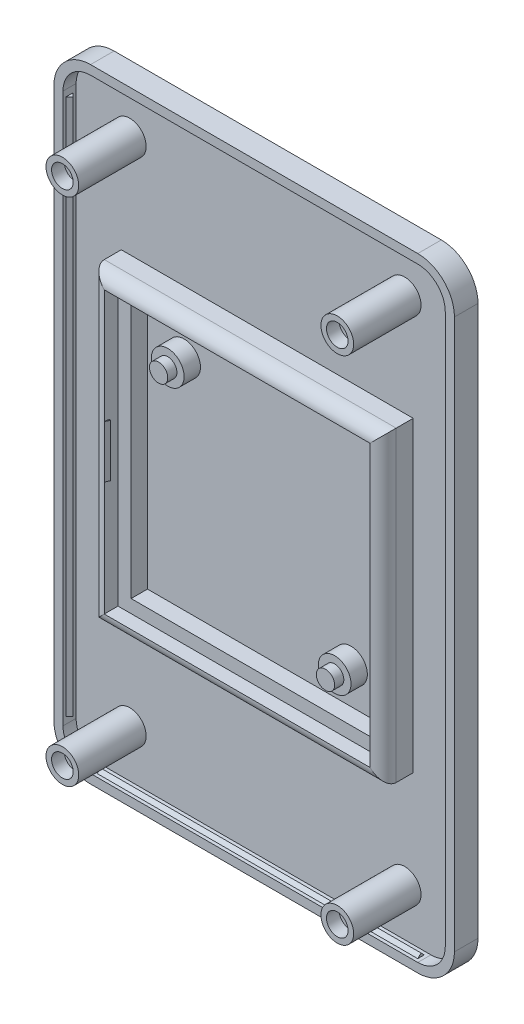
SolidWorks part; units mm, degrees
ref_plane "Front Plane" through (0, 0, 0) normal (0, 0, 1) x (1, 0, 0)
ref_plane "Top Plane" through (0, 0, 0) normal (0, 1, 0) x (1, 0, 0)
ref_plane "Right Plane" through (0, 0, 0) normal (1, 0, 0) x (0, 0, -1)
sketch "Esquisse2" plane through (0, 0, 0) normal (0, 0, 1) x (1, 0, 0)
  line L1 (-29.2, -46.2) -> (29.2, -46.2)
  line L2 (-29.2, -46.2) -> (-29.2, 46.2)
  line L3 (-29.2, 46.2) -> (29.2, 46.2)
  line L4 (29.2, -46.2) -> (29.2, 46.2)
  line L5 (-29.2, -46.2) -> (29.2, 46.2) construction
  line L6 (-29.2, 46.2) -> (29.2, -46.2) construction
  point P0 (0, 0)
  dimension "D1" = 92.4
  dimension "D2" = 58.4
extrude "Boss.-Extru.1" add sketch "Esquisse2" against normal blind 1.6
fillet "Congé1" radius 4.2 4 edges at (-29.2, 46.2, -0.8) (29.2, 46.2, -0.8) (29.2, -46.2, -0.8) (-29.2, -46.2, -0.8)
sketch "Esquisse3" plane through (0, 0, 0) normal (0, 0, 1) x (1, 0, 0)
  line L1 (20.3, -21.45) -> (-20.3, -21.45)
  line L2 (20.3, -21.45) -> (20.3, 21.45)
  line L3 (20.3, 21.45) -> (-20.3, 21.45)
  line L4 (-20.3, -21.45) -> (-20.3, 21.45)
  line L5 (20.3, -21.45) -> (-20.3, 21.45) construction
  line L6 (20.3, 21.45) -> (-20.3, -21.45) construction
  point P0 (0, 0)
  dimension "D1" = 42.9
  dimension "D2" = 40.6
extrude "Extru.-Mince1" add sketch "Esquisse3" along normal blind 2.5 thin contours L4 L3 L2 L1 thin type one direction reverse wall 2
sketch "Esquisse4" plane through (0, 0, 0) normal (0, 0, 1) x (1, 0, 0)
  line L0 (20.3, 21.45) -> (-20.3, 21.45) construction
  line L1 (-12.7, 13.95) -> (-20.2, 13.95)
  line L2 (-12.7, 13.95) -> (-12.7, 21.45)
  line L3 (-12.7, 21.45) -> (-20.2, 21.45)
  line L4 (-20.2, 13.95) -> (-20.2, 21.45)
  line L5 (-12.7, 13.95) -> (-20.2, 21.45) construction
  line L6 (-12.7, 21.45) -> (-20.2, 13.95) construction
  circle A0 centre (-12.7, 13.95) radius 2.5
  point P0 (-16.45, 17.7)
  dimension "D1" = 7.5
  dimension "D2" = 7.5
extrude "Boss.-Extru.2" add sketch "Esquisse4" along normal blind 2.5 contours A0
sketch "Esquisse5" plane through (0, 0, 0) normal (0, 0, 1) x (1, 0, 0)
  circle A0 centre (-12.7, 13.95) radius 1.4
extrude "Boss.-Extru.3" add sketch "Esquisse5" along normal blind 3.9
sketch "Esquisse6" plane through (0, 0, 0) normal (0, 0, 1) x (1, 0, 0)
  line L1 (20.3, -21.45) -> (12.8, -21.45) construction
  line L2 (20.3, -21.45) -> (20.3, -13.95) construction
  line L3 (20.3, -13.95) -> (12.8, -13.95) construction
  line L4 (12.8, -21.45) -> (12.8, -13.95)
  circle A0 centre (12.8, -13.95) radius 2.5
  dimension "D1" = 7.5
  dimension "D2" = 7.5
extrude "Boss.-Extru.4" add sketch "Esquisse6" along normal blind 2.5 contours A0
sketch "Esquisse7" plane through (0, 0, 0) normal (0, 0, 1) x (1, 0, 0)
  circle A0 centre (12.8, -13.95) radius 1.4
extrude "Boss.-Extru.5" add sketch "Esquisse7" along normal blind 3.9 contours A0
sketch "Esquisse8" plane through (0, 0, 0) normal (0, 0, 1) x (1, 0, 0)
  line L1 (20.3, -21.45) -> (-20.3, -21.45)
  line L2 (20.3, -21.45) -> (20.3, 21.45)
  line L3 (20.3, 21.45) -> (-20.3, 21.45)
  line L4 (-20.3, -21.45) -> (-20.3, 21.45)
extrude "Extru.-Mince2" add sketch "Esquisse8" along normal blind 4.6 thin thin type one direction wall 2
fillet "Congé2" radius 2 4 edges at (22.3, 0, 4.6) (0, 23.45, 4.6) (-22.3, 0, 4.6) (0, -23.45, 4.6)
sketch "Esquisse10" plane through (0, 0, 0) normal (0, 0, 1) x (1, 0, 0)
  line L1 (21, -39) -> (-21, -39)
  line L2 (21, -39) -> (21, 39)
  line L3 (21, 39) -> (-21, 39)
  line L4 (-21, -39) -> (-21, 39)
  line L5 (21, -39) -> (-21, 39) construction
  line L6 (21, 39) -> (-21, -39) construction
  circle A0 centre (21, -39) radius 2.5
  circle A1 centre (-21, -39) radius 2.5
  circle A2 centre (-21, 39) radius 2.5
  circle A3 centre (21, 39) radius 2.5
  point P0 (0, 0)
  dimension "D1" = 78
  dimension "D2" = 42
extrude "Boss.-Extru.6" add sketch "Esquisse10" along normal blind 10.3 contours A1 | A0 | A3 | A2
sketch "Esquisse13" plane through (0, 0, 10.3) normal (0, 0, 1) x (1, 0, 0)
  circle A0 centre (21, -39) radius 1.65
  circle A1 centre (-21, -39) radius 1.65
  circle A2 centre (-21, 39) radius 1.65
  circle A3 centre (21, 39) radius 1.65
extrude "Enlèv. mat.-Extru.1" cut sketch "Esquisse13" against normal blind 1.95
sketch "Esquisse14" plane through (0, 0, 0) normal (0, 0, 1) x (1, 0, 0)
  line L0 (25, 46.2) -> (-25, 46.2) construction
  line L1 (29.2, -42) -> (29.2, 42) construction
  line L2 (-29.2, 42) -> (-29.2, -42) construction
  line L3 (-25, -46.2) -> (25, -46.2) construction
  line L4 (25, 46.2) -> (-25, 46.2)
  line L5 (29.2, -42) -> (29.2, 42)
  line L6 (-29.2, 42) -> (-29.2, -42)
  line L7 (-25, -46.2) -> (25, -46.2)
  arc A0 (-25, 46.2) -> (-29.2, 42) centre (-25, 42) ccw construction
  arc A1 (29.2, 42) -> (25, 46.2) centre (25, 42) ccw construction
  arc A2 (25, -46.2) -> (29.2, -42) centre (25, -42) ccw construction
  arc A3 (-29.2, -42) -> (-25, -46.2) centre (-25, -42) ccw construction
  arc A4 (-25, 46.2) -> (-29.2, 42) centre (-25, 42) ccw
  arc A5 (29.2, 42) -> (25, 46.2) centre (25, 42) ccw
  arc A6 (25, -46.2) -> (29.2, -42) centre (25, -42) ccw
  arc A7 (-29.2, -42) -> (-25, -46.2) centre (-25, -42) ccw
extrude "Extru.-Mince3" add sketch "Esquisse14" along normal blind 2 and the other way blind 1.6 thin thin type one direction wall 1.4
sketch3d "Esquisse3D7"
  line L0 (20.3, -21.45, 4.6) -> (20.3, 0, 4.6) construction
  line L1 (20.3, -21.45, 4.6) -> (20.3, 21.45, 4.6) construction
  line L2 (20.3, 0, 4.6) -> (20.3, 0, 3.9)
  line L3 (20.3, 0, 4.6) -> (20.05, 0, 3.9)
  line L4 (20.05, 0, 3.9) -> (20.3, 0, 3.9)
extrude "Boss.-Extru.9" add sketch "Esquisse3D7" along direction (0, 1, 0) on the side of the normal blind 4 and the other way blind 4 contours L3 L4 L2
sketch3d "Esquisse3D8"
  line L0 (-20.3, 0, 4.6) -> (-20.0062, 0, 3.9153)
  line L1 (-20.3, 21.45, 4.6) -> (-20.3, -21.45, 4.6) construction
  line L2 (-20.0062, 0, 3.9153) -> (-20.2371, 0, 3.8947)
  line L3 (-20.2371, 0, 3.8947) -> (-20.3, 0, 4.6)
extrude "Boss.-Extru.10" add sketch "Esquisse3D8" along direction (0, -1, 0) on the side of the normal blind 4 and the other way blind 4 separate body
sketch "Esquisse16" plane through (29.2, 0, 0) normal (-1, 0, 0) x (0, 0, 1)
  line L0 (2, 0) -> (0, 0)
  line L1 (2, -42) -> (2, 42) construction
  line L2 (0, -42) -> (0, 42) construction
sketch3d "Esquisse3D9"
  line L2 (29.2, 0, 1) -> (29.2, 0, 1.5111)
  line L3 (29.2, 0, 2) -> (29.2, 0, 0) construction
  line L4 (29.2, 0, 1) -> (29.2, 0, 0.4889)
  line L6 (20.3, -21.45, 4.6) -> (20.3, -4, 4.6) construction
  line L7 (29.2, 0, 1.5111) -> (28.6889, 0, 1)
  line L8 (28.6889, 0, 1) -> (29.2, 0, 0.4889)
extrude "Boss.-Extru.11" add sketch "Esquisse3D9" along direction (0, 1, 0) on the side of the normal blind 41 and the other way blind 41
mirror "Symétrie1" about plane through (0, 0, 0) normal (1, 0, 0) of "Boss.-Extru.11"
sketch "Esquisse19" plane through (0, 46.2, 0) normal (0, -1, 0) x (-1, 0, 0)
  line L0 (0, -2) -> (0, 0) construction
  line L1 (-25, -2) -> (25, -2) construction
  line L2 (-25, 0) -> (25, 0) construction
  line L3 (0, -1) -> (0, -1.5)
  line L4 (0, -1) -> (0, -0.5)
sketch3d "Esquisse3D12"
  line L2 (0, 46.2, 1.5) -> (0, 45.7, 1)
  line L3 (0, 45.7, 1) -> (0, 46.2, 0.5)
  line L5 (0, 46.2, 1.5) -> (0, 46.2, 0.5)
  dimension "D1" = 90
extrude "Boss.-Extru.12" add sketch "Esquisse3D12" along direction (-1, 0, 0) on the side of the normal blind 24.5 and the other way blind 24.5
mirror "Symétrie2" about plane through (0, 0, 0) normal (0, 1, 0) of "Boss.-Extru.12"
sketch "Esquisse31" plane through (0, 0, -1.6) normal (0, 0, -1) x (-1, 0, 0)
  spline S0 degree 3 poles (4.0392, -9.9887) (3.6583, -9.8345) (3.3861, -9.4898) (3.3227, -9.0816) knots 0 0 0 0 1 1 1 1
  spline S1 degree 3 poles (3.3227, -9.0816) (3.2773, -8.8458) (3.3227, -8.6825) (3.6855, -8.0295) knots 1 1 1 1 2 2 2 2
  spline S2 degree 3 poles (3.6855, -8.0295) (5.046, -5.5805) (5.7444, -2.8141) (5.7081, -0.0113) knots 2 2 2 2 3 3 3 3
  spline S3 degree 3 poles (5.7081, -0.0113) (5.7444, 2.7098) (5.0823, 5.3673) (3.7762, 7.7528) knots 3 3 3 3 4 4 4 4
  spline S4 degree 3 poles (3.7762, 7.7528) (3.5857, 8.1519) (3.4134, 8.5329) (3.2682, 8.941) knots 4 4 4 4 5 5 5 5
  spline S5 degree 3 poles (3.2682, 8.941) (3.3227, 9.2857) (3.495, 9.6032) (3.7762, 9.7937) knots 5 5 5 5 6 6 6 6
  spline S6 degree 3 poles (3.7762, 9.7937) (4.1843, 10.0113) (4.6832, 9.966) (5.0551, 9.712) knots 6 6 6 6 7 7 7 7
  spline S7 degree 3 poles (5.0551, 9.712) (5.309, 9.3855) (5.5267, 9.059) (5.7081, 8.678) knots 7 7 7 7 8 8 8 8
  spline S8 degree 3 poles (5.7081, 8.678) (6.6877, 6.7914) (7.3499, 4.7959) (7.6764, 2.7098) knots 8 8 8 8 9 9 9 9
  spline S9 degree 3 poles (7.6764, 2.7098) (7.885, 1.068) (7.9122, -0.6009) (7.758, -2.2517) knots 9 9 9 9 10 10 10 10
  spline S10 degree 3 poles (7.758, -2.2517) (7.4768, -4.3741) (6.851, -6.424) (5.8895, -8.3379) knots 10 10 10 10 11 11 11 11
  spline S11 degree 3 poles (5.8895, -8.3379) (5.309, -9.4989) (4.9825, -9.9887) (4.6378, -9.9887) knots 11 11 11 11 12 12 12 12
  spline S12 degree 3 poles (4.6378, -9.9887) (4.5653, -9.9887) (4.4837, -9.9887) (4.4111, -9.9887) knots 12 12 12 12 13 13 13 13
  spline S13 degree 3 poles (4.4111, -9.9887) (4.2841, -9.9887) (4.1662, -9.9887) (4.0392, -9.9887) knots 13 13 13 13 14 14 14 14
  spline S14 degree 3 poles (0.0846, -7.9388) (0.0846, -7.9539) (0.0846, -7.969) (0.0846, -7.9841) knots 9 9 9 9 10 10 10 10
  spline S15 degree 3 poles (2.1344, -5.907) (1.3725, -7.6213) (0.8374, -8.1746) (0.0846, -7.9388) knots 8 8 8 8 9 9 9 9
  spline S16 degree 3 poles (2.6424, 4.5782) (3.8034, 1.1406) (3.622, -2.6054) (2.1344, -5.907) knots 7 7 7 7 8 8 8 8
  spline S17 degree 3 poles (1.0914, 7.6984) (1.7444, 6.737) (2.2614, 5.6848) (2.6424, 4.5782) knots 6 6 6 6 7 7 7 7
  spline S18 degree 3 poles (-0.4597, 7.5714) (-0.0606, 8.0159) (0.6016, 8.0794) (1.0914, 7.6984) knots 5 5 5 5 6 6 6 6
  spline S19 degree 3 poles (-0.1876, 5.7574) (-0.759, 6.9002) (-0.7953, 7.0816) (-0.4597, 7.5714) knots 4 4 4 4 5 5 5 5
  spline S20 degree 3 poles (1.2093, 1.0227) (1.0823, 2.6825) (0.6016, 4.2971) (-0.1876, 5.7574) knots 3 3 3 3 4 4 4 4
  spline S21 degree 3 poles (-0.115, -5.6712) (0.9553, -3.6122) (1.4179, -1.2902) (1.2093, 1.0227) knots 2 2 2 2 3 3 3 3
  spline S22 degree 3 poles (-0.6501, -6.7868) (-0.6501, -6.678) (-0.369, -6.1791) (-0.115, -5.6712) knots 1 1 1 1 2 2 2 2
  spline S23 degree 3 poles (0.0846, -7.9841) (-0.4324, -7.839) (-0.759, -7.3129) (-0.6501, -6.7868) knots 0 0 0 0 1 1 1 1
  spline S24 degree 3 poles (-3.9971, -5.907) (-3.9971, -5.9252) (-3.9971, -5.9433) (-3.9971, -5.9615) knots 10 10 10 10 11 11 11 11
  spline S25 degree 3 poles (-3.4801, -5.9887) (-3.6524, -6.0068) (-3.8338, -5.9887) (-3.9971, -5.907) knots 9 9 9 9 10 10 10 10
  spline S26 degree 3 poles (-2.2556, -4.7279) (-2.7454, -5.6803) (-2.9903, -5.907) (-3.4801, -5.9887) knots 8 8 8 8 9 9 9 9
  spline S27 degree 3 poles (-1.1037, -0.0113) (-1.0674, -1.6531) (-1.4665, -3.2857) (-2.2556, -4.7279) knots 7 7 7 7 8 8 8 8
  spline S28 degree 3 poles (-2.2646, 4.6054) (-1.4937, 3.1905) (-1.0946, 1.6032) (-1.1037, -0.0113) knots 6 6 6 6 7 7 7 7
  spline S29 degree 3 poles (-3.6615, 5.9116) (-3.081, 5.9116) (-2.7544, 5.6304) (-2.2646, 4.6054) knots 5 5 5 5 6 6 6 6
  spline S30 degree 3 poles (-4.3599, 5.6485) (-4.1876, 5.8481) (-3.9336, 5.9478) (-3.6615, 5.9116) knots 4 4 4 4 5 5 5 5
  spline S31 degree 3 poles (-4.251, 3.8345) (-4.8406, 4.9773) (-4.8406, 5.2132) (-4.3599, 5.6485) knots 3 3 3 3 4 4 4 4
  spline S32 degree 3 poles (-4.251, -4.0385) (-2.8996, -1.5896) (-2.8996, 1.3855) (-4.251, 3.8345) knots 2 2 2 2 3 3 3 3
  spline S33 degree 3 poles (-4.6592, -5.1814) (-4.6592, -5) (-4.6592, -4.7642) (-4.251, -4.0385) knots 1 1 1 1 2 2 2 2
  spline S34 degree 3 poles (-3.9971, -5.9615) (-4.3236, -5.8163) (-4.5685, -5.5261) (-4.6592, -5.1814) knots 0 0 0 0 1 1 1 1
  spline S35 degree 3 poles (-7.8066, -4.0295) (-7.8096, -4.0295) (-7.8126, -4.0295) (-7.8157, -4.0295) knots 9 9 9 9 10 10 10 10
  spline S36 degree 3 poles (-6.2737, -3.3039) (-6.7363, -4.0023) (-7.2624, -4.2109) (-7.8066, -4.0295) knots 8 8 8 8 9 9 9 9
  spline S37 degree 3 poles (-6.2737, 3.2902) (-4.9585, 1.2857) (-4.9585, -1.2993) (-6.2737, -3.3039) knots 7 7 7 7 8 8 8 8
  spline S38 degree 3 poles (-7.5617, 4.0975) (-7.0719, 4.1882) (-6.7272, 3.9796) (-6.2737, 3.2902) knots 6 6 6 6 7 7 7 7
  spline S39 degree 3 poles (-8.4687, 2.873) (-8.5685, 3.4444) (-8.1876, 3.9887) (-7.5617, 4.0975) knots 5 5 5 5 6 6 6 6
  spline S40 degree 3 poles (-8.0696, 2.1565) (-8.2238, 2.3832) (-8.3508, 2.6281) (-8.4687, 2.873) knots 4 4 4 4 5 5 5 5
  spline S41 degree 3 poles (-7.4801, -0.0113) (-7.4166, 0.7596) (-7.6252, 1.5215) (-8.0696, 2.1565) knots 3 3 3 3 4 4 4 4
  spline S42 degree 3 poles (-8.1059, -2.1519) (-7.6524, -1.5351) (-7.4347, -0.7732) (-7.4801, -0.0113) knots 2 2 2 2 3 3 3 3
  spline S43 degree 3 poles (-8.4687, -3.322) (-8.5594, -3.0045) (-8.4687, -2.7324) (-8.1059, -2.1519) knots 1 1 1 1 2 2 2 2
  spline S44 degree 3 poles (-7.8157, -4.0295) (-8.115, -3.8844) (-8.3508, -3.6395) (-8.4687, -3.322) knots 0 0 0 0 1 1 1 1
extrude "Enlèv. mat.-Extru.4" cut sketch "Esquisse31" against normal blind 0.4
sketch "Esquisse32" plane through (0, 0, -1.6) normal (0, 0, -1) x (-1, 0, 0)
  circle A0 centre (0, 0) radius 15.75
extrude "Enlèv. de mat.-Extru.-Mince1" cut sketch "Esquisse32" against normal blind 0.4 thin thin type one direction reverse wall 1
